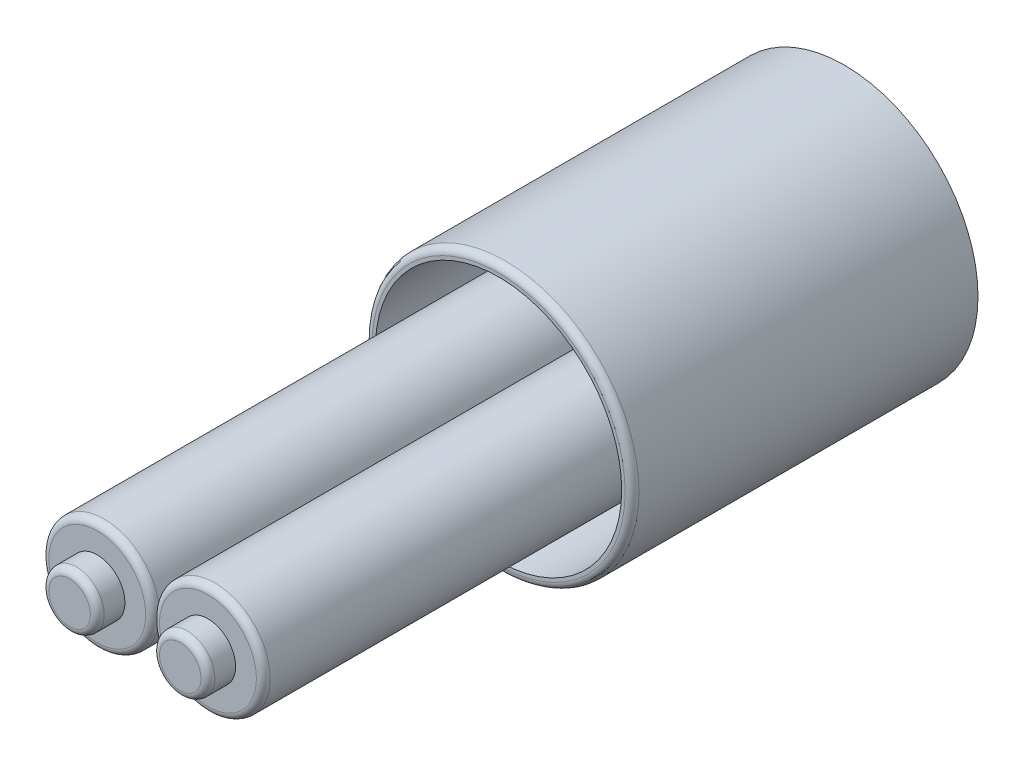
SolidWorks part; units mm, degrees
ref_plane "Front Plane" through (0, 0, 0) normal (0, 0, 1) x (1, 0, 0)
ref_plane "Top Plane" through (0, 0, 0) normal (0, 1, 0) x (1, 0, 0)
ref_plane "Right Plane" through (0, 0, 0) normal (1, 0, 0) x (0, 0, -1)
sketch "Sketch1" plane through (0, 0, 0) normal (0, 0, 1) x (1, 0, 0)
  line L5 (0, 0.1016) -> (0, -0.1016) construction
  line L6 (0.1016, 0) -> (-0.1016, 0) construction
  circle A0 centre (-0.1016, 0.1016) radius 0.1016
  circle A1 centre (0.1016, 0.1016) radius 0.1016
  circle A2 centre (0, 0.1016) radius 0.2261
  circle A3 centre (0, 0.1016) radius 0.2451
  circle A4 centre (-0.1016, 0.1016) radius 0.0508
  circle A5 centre (0.1016, 0.1016) radius 0.0508
  point P0 (0, 0)
extrude "Boss-Extrude3" add sketch "Sketch1<9>" along normal blind 1.27 separate body contours A0 A4 | A1 A5 region at (-0.2003, 0.1016, 0) region at (0.1016, 0.2003, 0)
sketch "Sketch1<9>" plane through (0, 0, 0) normal (0, 0, 1) x (1, 0, 0) same geometry as "Sketch1"
extrude "Boss-Extrude4" add sketch "Sketch1" along normal blind 0.635 contours A3 A2 region at (-0.2382, 0.1016, 0)
extrude "Boss-Extrude5" add sketch "Sketch1<12>" along normal blind 1.3208 separate body contours A4 region at (-0.1016, 0.1016, 0)
sketch "Sketch1<12>" plane through (0, 0, 0) normal (0, 0, 1) x (1, 0, 0) same geometry as "Sketch1"
fillet "Fillet3" radius 0.0127 1 edges at (-0.0508, 0.1016, 1.3208)
extrude "Boss-Extrude7" add sketch "Sketch1<14>" along normal blind 1.3208 separate body contours A5 region at (0.1016, 0.1016, 0)
sketch "Sketch1<14>" plane through (0, 0, 0) normal (0, 0, 1) x (1, 0, 0) same geometry as "Sketch1"
fillet "Fillet4" radius 0.0127 1 edges at (0.1524, 0.1016, 1.3208)
fillet "Fillet5" radius 0.0127 1 edges at (0.2032, 0.1016, 1.27)
fillet "Fillet6" radius 0.0127 1 edges at (0, 0.1016, 1.27)
fillet "Fillet11" radius 0.0127 1 edges at (0.2451, 0.1016, 0.635)
